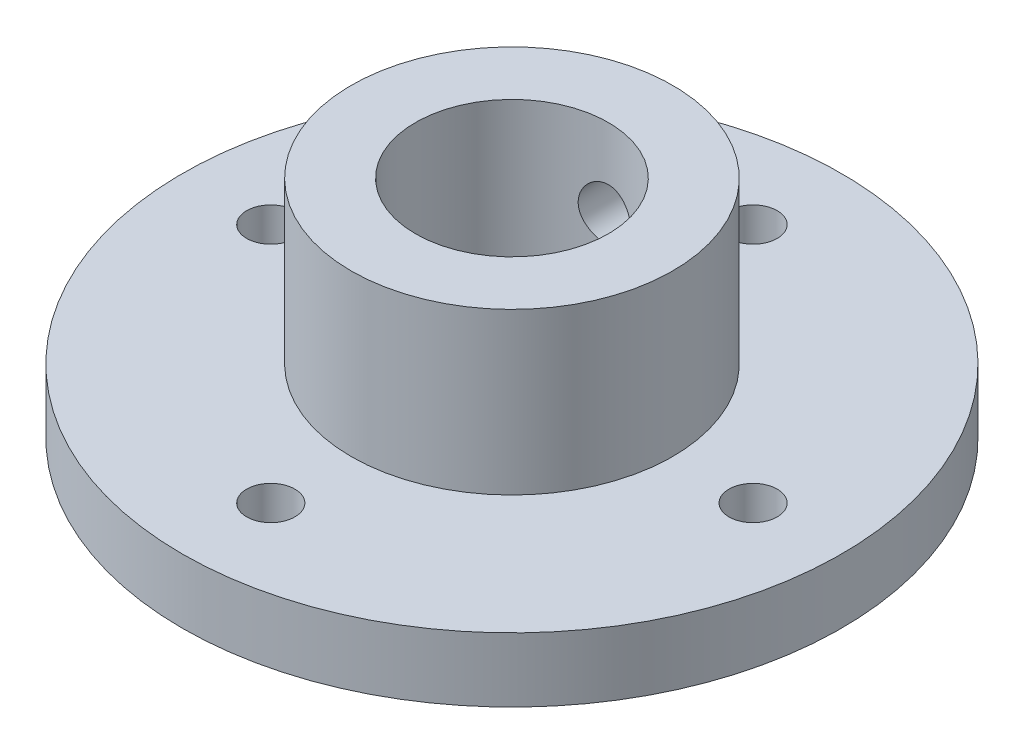
SolidWorks part; units mm, degrees
ref_plane "前视基准面" through (0, 0, 0) normal (0, 0, 1) x (1, 0, 0)
ref_plane "上视基准面" through (0, 0, 0) normal (0, 1, 0) x (1, 0, 0)
ref_plane "右视基准面" through (0, 0, 0) normal (1, 0, 0) x (0, 0, -1)
sketch "Sketch1" plane through (0, 0, 0) normal (1, 0, 0) x (0, 0, -1)
  line L0 (6, 0) -> (6, -14)
  line L1 (6, -14) -> (20.5, -14)
  line L2 (20.5, -14) -> (20.5, -10)
  line L3 (20.5, -10) -> (10, -10)
  line L4 (10, -10) -> (10, 0)
  line L5 (10, 0) -> (6, 0)
  line L6 (0, 12.4625) -> (0, -20.7921) construction
  dimension "D1" = 14
  dimension "D2" = 10
  dimension "D3" = 6
  dimension "D4" = 10
  dimension "D5" = 20.5
revolve "Revolve1" add sketch "Sketch1" angle 360 about L6
sketch "Sketch4" plane through (0, -10, 0) normal (0, 1, 0) x (1, 0, 0)
  circle A0 centre (0, 0) radius 15 construction
  circle A1 centre (0, 15) radius 1.5
  circle A2 centre (15, 0) radius 1.5
  circle A3 centre (0, -15) radius 1.5
  circle A4 centre (-15, 0) radius 1.5
  dimension "D1" = 4
extrude "Cut-Extrude1" cut sketch "Sketch4" against normal up to next
hole_wizard "M4 Tapped Hole1" positions "3DSketch1" profile "Sketch7" tap size "M4" standard "DIN" end condition up to next
sketch3d "3DSketch1"
  line L0 (0, 0, 0) -> (0, -5, 0) construction
  line L1 (0, -5, 0) -> (0, -5, -10) construction
  point P0 (0, -5, -10)
sketch "Sketch7" plane through (0, -5, -10) normal (1, 0, 0) x (0, 1, 0)
  line L0 (0, 0) -> (0, 4)
  line L1 (0, 4) -> (1.65, 4)
  line L2 (1.65, 4) -> (1.65, 0)
  line L5 (1.65, 0) -> (0, 0)
  line L11 (0, -6.35) -> (0, 107.95) construction
  dimension "Thru Tap Drill Dia." = 3.3
  dimension "Thru Tap Drill Depth" = 4
cosmetic thread "Hole Thread1"
